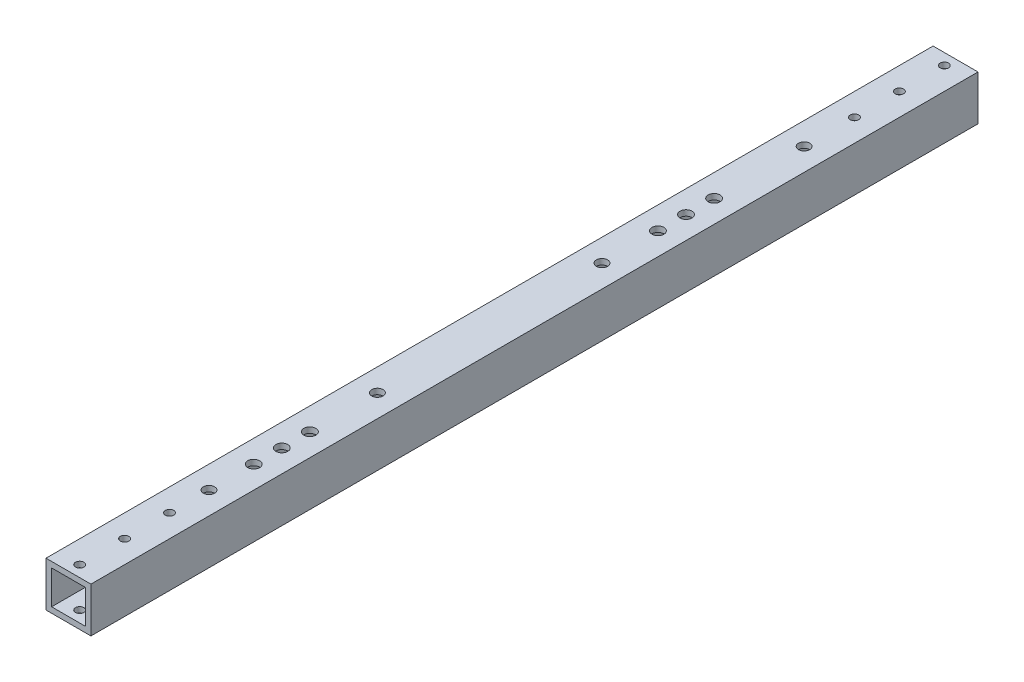
SolidWorks part; units mm, degrees
material "6061-T6 (SS)"
ref_plane "Front Plane" through (0, 0, 0) normal (0, 0, 1) x (1, 0, 0)
ref_plane "Top Plane" through (0, 0, 0) normal (0, 1, 0) x (1, 0, 0)
ref_plane "Right Plane" through (0, 0, 0) normal (1, 0, 0) x (0, 0, -1)
sketch "Sketch1" plane through (0, 0, 0) normal (0, 0, 1) x (1, 0, 0)
  line L1 (-12.7, -12.7) -> (12.7, -12.7)
  line L2 (-12.7, -12.7) -> (-12.7, 12.7)
  line L3 (-12.7, 12.7) -> (12.7, 12.7)
  line L4 (12.7, -12.7) -> (12.7, 12.7)
  line L5 (-12.7, -12.7) -> (12.7, 12.7) construction
  line L6 (-12.7, 12.7) -> (12.7, -12.7) construction
  point P0 (0, 0)
  dimension "D1" = 25.4
  dimension "D2" = 25.4
extrude "Extrude-Thin1" add sketch "Sketch1" along normal blind 501.65 thin thin type one direction reverse wall 3.175
hole_wizard "3/16 (0.1875) Diameter Hole1" positions "3DSketch1" profile "Sketch3" hole size "3/16" standard "ANSI Inch" end condition through all
sketch3d "3DSketch1"
  line L1 (12.7, 12.7, 0) -> (-12.7, 12.7, 0) construction
  line L6 (0, 12.7, 501.65) -> (0, 12.7, 0) construction
  line L7 (12.7, 12.7, 501.65) -> (-12.7, 12.7, 501.65) construction
  point P57 (0, 12.7, 6.35)
  point P59 (0, 12.7, 31.75)
  point P61 (0, 12.7, 57.15)
  point P63 (0, 12.7, 469.9)
  point P65 (0, 12.7, 444.5)
  point P67 (0, 12.7, 495.3)
  dimension "D1" = 25.4
  dimension "D2" = 25.4
  dimension "D3" = 6.35
  dimension "D4" = 25.4
  dimension "D5" = 25.4
  dimension "D6" = 6.35
sketch "Sketch3" plane through (0, 12.7, 495.3) normal (1, 0, 0) x (0, 0, 1)
  line L0 (0, 0) -> (0, 25.4)
  line L1 (0, 25.4) -> (2.3812, 25.4)
  line L2 (2.3812, 25.4) -> (2.3812, 0)
  line L5 (2.3812, 0) -> (0, 0)
  line L11 (0, -6.35) -> (0, 107.95) construction
  dimension "Thru Hole Dia." = 4.7625
  dimension "Thru Hole Depth" = 25.4
hole_wizard "1/4 (0.25) Diameter Hole1" positions "Sketch6" profile "Sketch7" hole size "1/4" standard "ANSI Inch"
sketch "Sketch6" plane through (0, 12.7, 0) normal (0, 1, 0) x (1, 0, 0)
  point P0 (0, -199.9335)
  point P15 (0, -422.2)
  point P23 (0, -326.95)
  point P26 (0, -85.6235)
sketch "Sketch7" plane through (0, 12.7, 199.9335) normal (1, 0, 0) x (0, 0, 1)
  line L0 (0, 0) -> (0, 27.3077)
  line L1 (0, 27.3077) -> (3.175, 25.4)
  line L2 (3.175, 25.4) -> (3.175, 0)
  line L5 (3.175, 0) -> (0, 0)
  line L10 (0, 27.3077) -> (-3.175, 25.4) construction
  line L11 (0, -6.35) -> (0, 107.95) construction
  dimension "Hole Dia." = 6.35
  dimension "Hole Depth" = 25.4
  dimension "Drill Angle" = 118
hole_wizard "1/4 Clearance Hole1" positions "Sketch17" profile "Sketch18" hole size "1/4" standard "ANSI Inch"
sketch "Sketch17" plane through (-381, 12.7, 250.825) normal (0, 1, 0) x (1, 0, 0)
  point P0 (381, 82.55)
  point P3 (381, 98.425)
  point P6 (381, 114.3)
  point P9 (381, -146.05)
  point P12 (381, -130.175)
  point P15 (381, -114.3)
  point P18 (-381, -146.05)
  point P21 (-381, -130.175)
  point P24 (-381, -114.3)
  point P27 (-381, 82.55)
  point P30 (-381, 98.425)
  point P33 (-381, 114.3)
sketch "Sketch18" plane through (0, 12.7, 168.275) normal (1, 0, 0) x (0, 0, 1)
  line L0 (0, 0) -> (0, 40.1298)
  line L1 (0, 40.1298) -> (3.3782, 38.1)
  line L2 (3.3782, 38.1) -> (3.3782, 0)
  line L3 (3.3782, 0) -> (0, 0)
  line L4 (0, 40.1298) -> (-3.3782, 38.1) construction
  line L5 (0, -6.35) -> (0, 107.95) construction
  dimension "Hole Dia." = 6.7564
  dimension "Hole Depth" = 38.1
  dimension "Drill Angle" = 118
